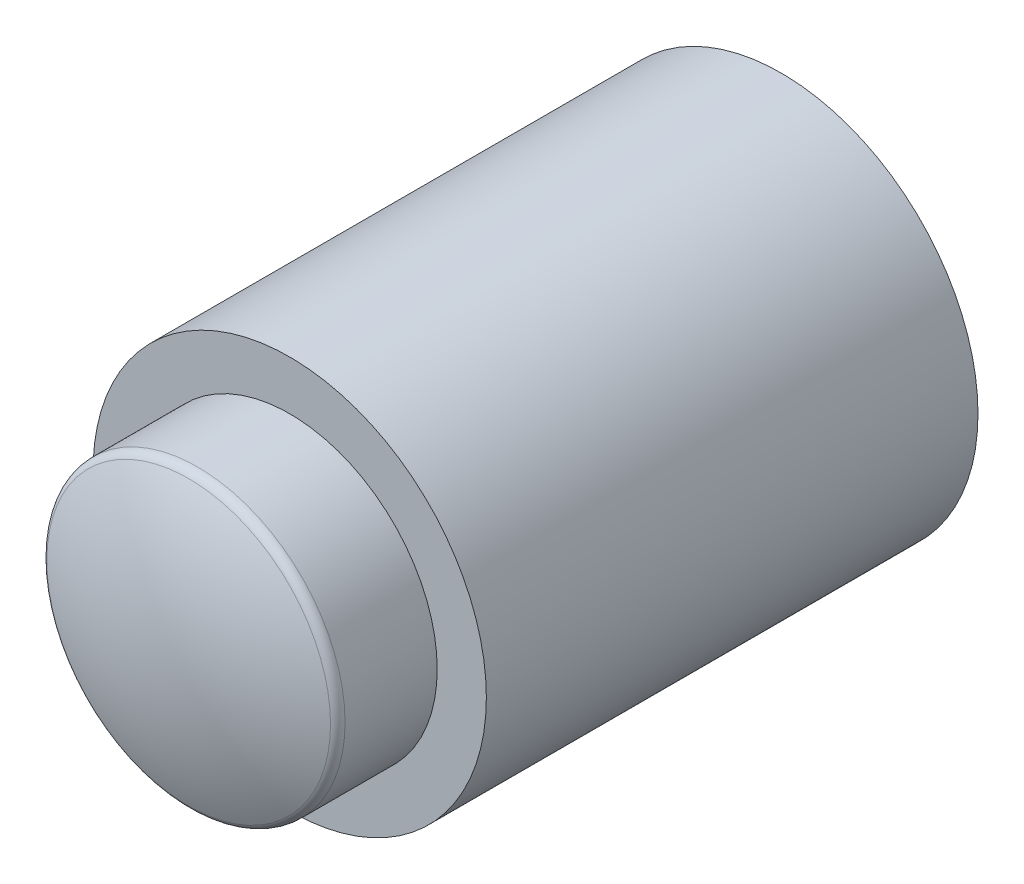
SolidWorks part; units mm, degrees
ref_plane "Front Plane" through (0, 0, 0) normal (0, 0, 1) x (1, 0, 0)
ref_plane "Top Plane" through (0, 0, 0) normal (0, 1, 0) x (1, 0, 0)
ref_plane "Right Plane" through (0, 0, 0) normal (1, 0, 0) x (0, 0, -1)
sketch "Sketch1" plane through (0, 0, 0) normal (0, 0, 1) x (1, 0, 0)
  circle A0 centre (0, 0) radius 30
  dimension "D1" = 60
extrude "Boss-Extrude1" add sketch "Sketch1" along normal blind 20
dome "Dome1" faces to dome 1 distance 7 reverse direction no elliptical dome no face at (30, 0, 20) parameters "D1"=7
sketch "Sketch2" plane through (0, 0, 0) normal (0, 0, -1) x (-1, 0, 0)
  circle A3 centre (0, 0) radius 40
  circle A4 centre (0, 0) radius 40
  dimension "D1" = 10
extrude "Boss-Extrude2" add sketch "Sketch2" along normal blind 100
fillet "Fillet1" radius 2 1 edges at (30, 0, 20)
